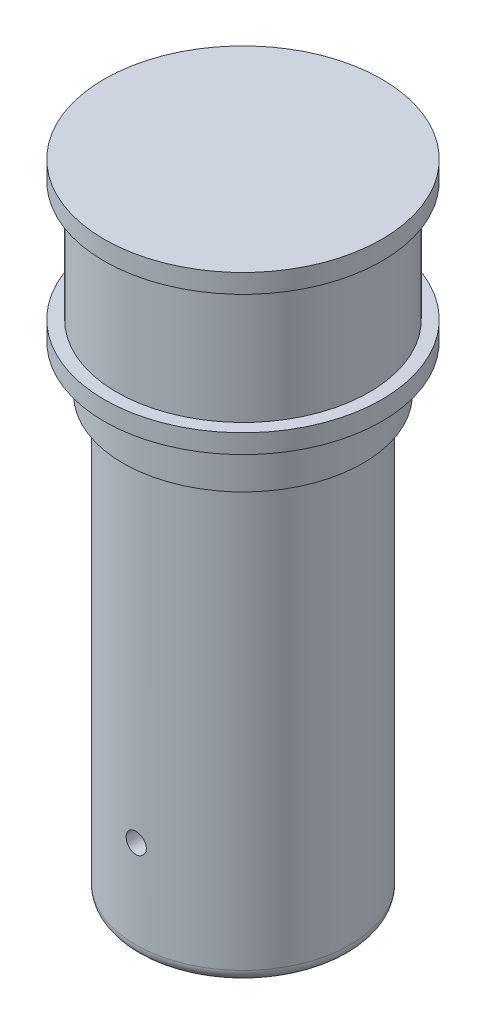
SolidWorks part; units mm, degrees
material "ABS"
ref_plane "Front Plane" through (0, 0, 0) normal (0, 0, 1) x (1, 0, 0)
ref_plane "Top Plane" through (0, 0, 0) normal (0, 1, 0) x (1, 0, 0)
ref_plane "Right Plane" through (0, 0, 0) normal (1, 0, 0) x (0, 0, -1)
sketch "Sketch1" plane through (0, 0, 0) normal (0, 0, 1) x (1, 0, 0)
  line L2 (-8.5, -38.175) -> (-8.5, -3.625)
  line L3 (-9.5, 0) -> (-11, 0)
  line L4 (-11, 0) -> (-11, 1.5)
  line L5 (-11, 1.5) -> (-10, 1.5)
  line L6 (-10, 1.5) -> (-10, 11)
  line L7 (-10, 11) -> (-11, 11)
  line L8 (-11, 11) -> (-11, 12.5)
  line L9 (-11, 12.5) -> (0, 12.5)
  line L10 (0, 12.5) -> (0, -24.175)
  line L11 (-4, -38.175) -> (-8.5, -38.175)
  line L12 (-4, -24.175) -> (-4, -38.175)
  line L13 (0, -24.175) -> (-4, -24.175)
  line L14 (-8.5, -3.625) -> (-9.5, -3.625)
  line L15 (-9.5, -3.625) -> (-9.5, 0)
  dimension "D1" = 8.5
  dimension "D2" = 1
  dimension "D3" = 38.175
  dimension "D4" = 1.5
  dimension "D5" = 4
  dimension "D6" = 14
  dimension "D7" = 12.5
  dimension "D8" = 10
  dimension "D9" = 34.55
  dimension "D10" = 1
revolve "Revolve1" add sketch "Sketch1" angle 360 about L10
fillet "Fillet1" radius 1 2 edges at (-8.5, -38.175, 0) (-4, -38.175, 0)
hole_wizard "M2x0.4 Tapped Hole1" positions "Sketch2" profile "Sketch3" tap size "M2x0.4" standard "ANSI Metric" end condition up to next
sketch "Sketch2" plane through (0, 0, 0) normal (0, 0, 1) x (1, 0, 0)
  line L0 (-7.5, -38.175) -> (7.5, -38.175) construction
  point P0 (0, -30.175)
  dimension "D1" = 8
sketch "Sketch3" plane through (0, -30.175, 0) normal (1, 0, 0) x (0, 1, 0)
  line L0 (0, 0) -> (0, 8.5)
  line L1 (0, 8.5) -> (0.8, 8.5)
  line L2 (0.8, 8.5) -> (0.8, 0)
  line L5 (0.8, 0) -> (0, 0)
  line L11 (0, -6.35) -> (0, 107.95) construction
  dimension "Thru Tap Drill Dia." = 1.6
  dimension "Thru Tap Drill Depth" = 8.5
cosmetic thread "Hole Thread1" parameters "D2"=2
